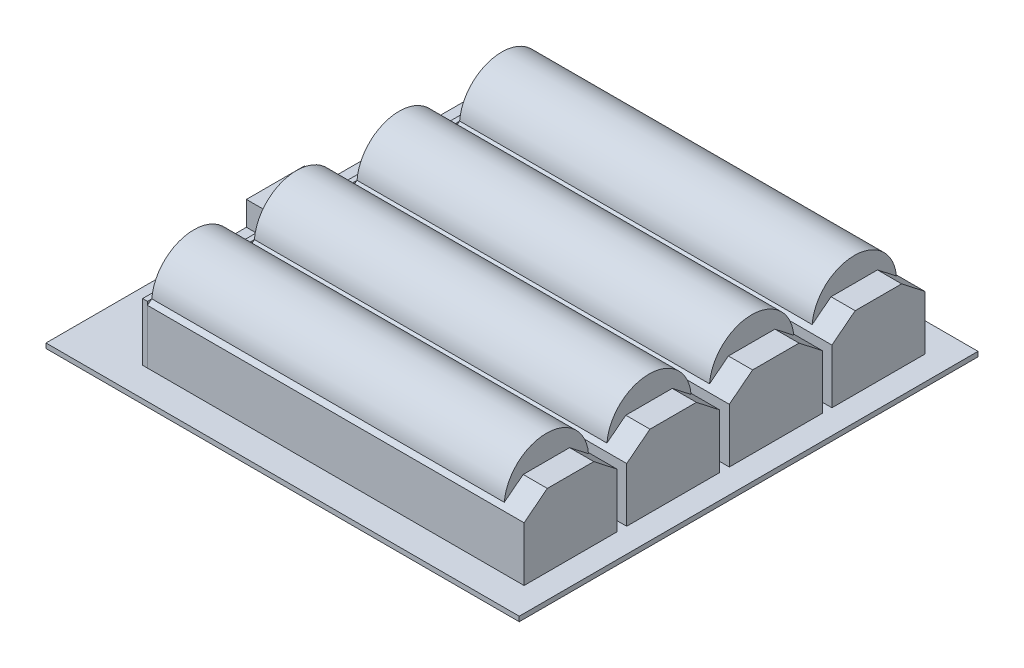
SolidWorks part; units mm, degrees
ref_plane "정면" through (0, 0, 0) normal (0, 0, 1) x (1, 0, 0)
ref_plane "윗면" through (0, 0, 0) normal (0, 1, 0) x (1, 0, 0)
ref_plane "우측면" through (0, 0, 0) normal (1, 0, 0) x (0, 0, -1)
sketch "스케치1" plane through (0, 0, 0) normal (0, 1, 0) x (1, 0, 0)
  line L1 (-49, 47.5) -> (49, 47.5)
  line L2 (-49, 47.5) -> (-49, -47.5)
  line L3 (-49, -47.5) -> (49, -47.5)
  line L4 (49, 47.5) -> (49, -47.5)
  line L5 (-49, 47.5) -> (49, -47.5) construction
  line L6 (-49, -47.5) -> (49, 47.5) construction
  point P0 (0, 0)
  dimension "D1" = 98
  dimension "D2" = 95
extrude "보스-돌출1" add sketch "스케치1" along normal blind 1
sketch "스케치2" plane through (0, 1, 0) normal (0, 1, 0) x (1, 0, 0)
  line L1 (-49, 47.5) -> (49, 47.5)
  line L2 (-49, 47.5) -> (-49, -47.5)
  line L3 (-49, -47.5) -> (49, -47.5)
  line L4 (49, 47.5) -> (49, -47.5)
  line L5 (-34, 42.5) -> (44, 42.5)
  line L6 (-34, 42.5) -> (-34, -42.5)
  line L7 (-34, -42.5) -> (44, -42.5)
  line L8 (44, 42.5) -> (44, -42.5)
  line L9 (-34, 42.5) -> (44, 42.5)
  line L10 (-34, 42.5) -> (-34, -42.5)
  line L11 (-34, -42.5) -> (44, -42.5)
  line L12 (44, 42.5) -> (44, -42.5)
  dimension "D1" = 5
  dimension "D2" = 5
  dimension "D3" = 15
  dimension "D4" = 5
  dimension "D5" = 85
  dimension "D6" = 78
extrude "보스-돌출2" add sketch "스케치2" along normal blind 20 contours L8 L5 L6 L7 region at (5, 1, 0)
sketch "스케치4" plane through (44, 0, 0) normal (1, 0, 0) x (0, 0, -1)
  line L0 (0, 21) -> (0, 1) construction
  line L1 (42.5, 21) -> (-42.5, 21) construction
  line L2 (42.5, 1) -> (-42.5, 1) construction
  line L3 (-42.5, 21) -> (0, 21) construction
  line L4 (-21.25, 21) -> (-21.25, 1) construction
  line L5 (21.25, 21) -> (21.25, 1) construction
  line L6 (-41.5, 1) -> (-22.25, 1)
  line L7 (-47.5, 1) -> (47.5, 1) construction
  line L8 (-1, 1) -> (-20.25, 1)
  line L9 (-42.5, 21) -> (-42.5, 1) construction
  line L11 (-41.5, 1) -> (-22.25, 1)
  line L12 (-41.5, 1) -> (-41.5, 12.2547)
  line L13 (-36.685, 16.0072) -> (-27.065, 16.0072)
  line L14 (-22.25, 1) -> (-22.25, 12.2547)
  line L15 (-1, 1) -> (-20.25, 1)
  line L18 (-31.875, 16.0072) -> (-31.875, 1) construction
  line L19 (-20.25, 1) -> (-20.25, 12.2547)
  line L20 (-41.5, 12.2547) -> (-36.685, 16.0072)
  line L21 (-22.25, 12.2547) -> (-27.065, 16.0072)
  line L22 (-1, 1) -> (-1, 12.2547)
  line L23 (-1, 12.2547) -> (-5.815, 16.0072)
  line L24 (-20.25, 12.2547) -> (-15.435, 16.0072)
  line L25 (-5.815, 16.0072) -> (-15.435, 16.0072)
  line L26 (22.25, 1) -> (22.25, 12.2547)
  line L27 (41.5, 1) -> (41.5, 12.2547)
  line L28 (41.5, 12.2547) -> (36.685, 16.0072)
  line L29 (22.25, 12.2547) -> (27.065, 16.0072)
  line L30 (36.685, 16.0072) -> (27.065, 16.0072)
  line L31 (1, 1) -> (1, 12.2547)
  line L32 (20.25, 1) -> (20.25, 12.2547)
  line L33 (20.25, 12.2547) -> (15.435, 16.0072)
  line L34 (1, 12.2547) -> (5.815, 16.0072)
  line L35 (5.815, 16.0072) -> (15.435, 16.0072)
  arc A0 (-23.1584, 12.9627) -> (-40.5916, 12.9627) centre (-31.875, 12.2547) ccw
  arc A1 (-19.3416, 12.9627) -> (-1.9084, 12.9627) centre (-10.625, 12.2547) cw
  arc A2 (23.1584, 12.9627) -> (40.5916, 12.9627) centre (31.875, 12.2547) cw
  arc A3 (19.3416, 12.9627) -> (1.9084, 12.9627) centre (10.625, 12.2547) ccw
  line M6 (-42.5, 1) -> (42.5, 1)
  line M7 (42.5, 1) -> (42.5, 21)
  line M8 (42.5, 21) -> (-42.5, 21)
  line M9 (-42.5, 21) -> (-42.5, 1)
  dimension "D1" = 1
  dimension "D2" = 1
extrude "컷-돌출1" cut sketch "스케치4" against normal blind 100 contours A0 L12 L20 M8 M9 M6 | L24 A1 A0 L21 L14 L19 M8 M6 | A3 A1 L23 L22 L31 L34 M8 M6 | A3 L33 L32 L26 L29 A2 M6 M8 | A2 L28 L27 M8 M6 M7 region at (44, 14.9934, 40.5935) region at (44, 14.9934, 21.25) region at (44, 14.9934, 0) region at (44, 14.9934, -21.25) region at (44, 14.9934, -40.5935)
extrude "컷-돌출2" cut sketch "스케치4<3>" against normal blind 5 contours L21 A0 L20 L13 | A1 L24 L25 L23 | L33 A3 L34 L35 | A2 L29 L30 L28 region at (44, 17.597, 31.875) region at (44, 17.597, 10.625) region at (44, 17.597, -31.875) region at (44, 17.597, -10.625)
sketch "스케치4<3>" plane through (44, 0, 0) normal (1, 0, 0) x (0, 0, -1) same geometry as "스케치4"
sketch "스케치5" plane through (0, 1, 0) normal (0, 1, 0) x (1, 0, 0)
  line L0 (-49, 47.5) -> (-49, -47.5) construction
  line L1 (-49, 6) -> (-40, 6)
  line L2 (-49, 6) -> (-49, -6)
  line L3 (-49, -6) -> (-40, -6)
  line L4 (-40, 6) -> (-40, -6)
  dimension "D1" = 41.5
  dimension "D2" = 41.5
  dimension "D3" = 9
extrude "보스-돌출3" add sketch "스케치5" along normal blind 5
sketch "스케치6" plane through (-49, 0, 0) normal (-1, 0, 0) x (0, 0, 1)
  line L0 (-6, 1) -> (6, 1) construction
  line L1 (0, 1) -> (0, 6) construction
  line L2 (-6, 6) -> (6, 6) construction
  line L3 (-5.6, 1) -> (-5.6, 5.6)
  line L4 (5.6, 1) -> (5.6, 5.6)
  line L5 (-5.6, 5.6) -> (5.6, 5.6)
  line L6 (5.1, 5.1747) -> (-5.1, 5.1747)
  line L7 (-5.1, 5.1747) -> (-5.1, 3.4256)
  line L8 (5.1, 5.1747) -> (5.1, 3.4256)
  line L9 (-5.1, 3.4256) -> (5.1, 3.4256)
  line L10 (-5.6, 1) -> (5.6, 1)
  point P12 (0, 5.6)
  point P16 (0, 5.1747)
  point P18 (0, 3.4256)
  dimension "D1" = 0.4
  dimension "D2" = 0.4
  dimension "D3" = 1.7491
  dimension "D4" = 10.2
extrude "컷-돌출4" cut sketch "스케치6" against normal blind 8
sketch "스케치7" plane through (0, 6, 0) normal (0, 1, 0) x (1, 0, 0)
  line L0 (-49, 0) -> (-40, 0) construction
  line L1 (-49, 6) -> (-49, -6) construction
  line L2 (-40, -6) -> (-40, 6) construction
  line L3 (-42.7314, 2.8369) -> (-46.2834, 2.8369)
  line L4 (-42.7314, -2.8369) -> (-46.2834, -2.8369)
  line L5 (-46.2834, 2.8369) -> (-47.2554, 2.4872)
  line L6 (-46.2834, -2.8369) -> (-47.2554, -2.4872)
  line L7 (-47.2554, 2.4872) -> (-47.2554, 1.3055)
  line L8 (-47.2554, -2.4872) -> (-47.2554, -1.3055)
  line L9 (-47.2554, 1.3055) -> (-46.3394, 0.6832)
  line L10 (-47.2554, -1.3055) -> (-46.3394, -0.6832)
  line L11 (-46.3394, 0.6832) -> (-42.7314, 0.6832)
  line L12 (-46.3394, -0.6832) -> (-42.7314, -0.6832)
  line L13 (-42.7314, 0.6832) -> (-42.7314, 0.9944)
  line L14 (-42.7314, -0.6832) -> (-42.7314, -0.9944)
  line L15 (-42.7314, 0.9944) -> (-46.3394, 0.9944)
  line L16 (-42.7314, -0.9944) -> (-46.3394, -0.9944)
  line L17 (-46.3394, 0.9944) -> (-46.9601, 1.4161)
  line L18 (-46.3394, -0.9944) -> (-46.9601, -1.4161)
  line L19 (-46.9601, 1.4161) -> (-46.9601, 2.3963)
  line L20 (-46.9601, -1.4161) -> (-46.9601, -2.3963)
  line L21 (-46.9601, 2.3963) -> (-46.3394, 2.6196)
  line L22 (-46.9601, -2.3963) -> (-46.3394, -2.6196)
  line L23 (-46.3394, 2.6196) -> (-42.7314, 2.6196)
  line L24 (-46.3394, -2.6196) -> (-42.7314, -2.6196)
  line L25 (-42.7314, 2.6196) -> (-42.7314, 2.8369)
  line L26 (-42.7314, -2.6196) -> (-42.7314, -2.8369)
extrude "컷-돌출5" cut sketch "스케치7" against normal blind 0.5
sketch "스케치8" plane through (-34, 0, 0) normal (-1, 0, 0) x (0, 0, 1)
  line L0 (22.25, 1) -> (41.5, 1) construction
  line L1 (-41.5, 12.9627) -> (41.5, 12.9627)
  line L2 (-41.5, 12.9627) -> (-41.5, 1)
  line L3 (-41.5, 1) -> (41.5, 1)
  line L4 (41.5, 12.9627) -> (41.5, 1)
extrude "보스-돌출4" add sketch "스케치8" along normal blind 1 separate body
